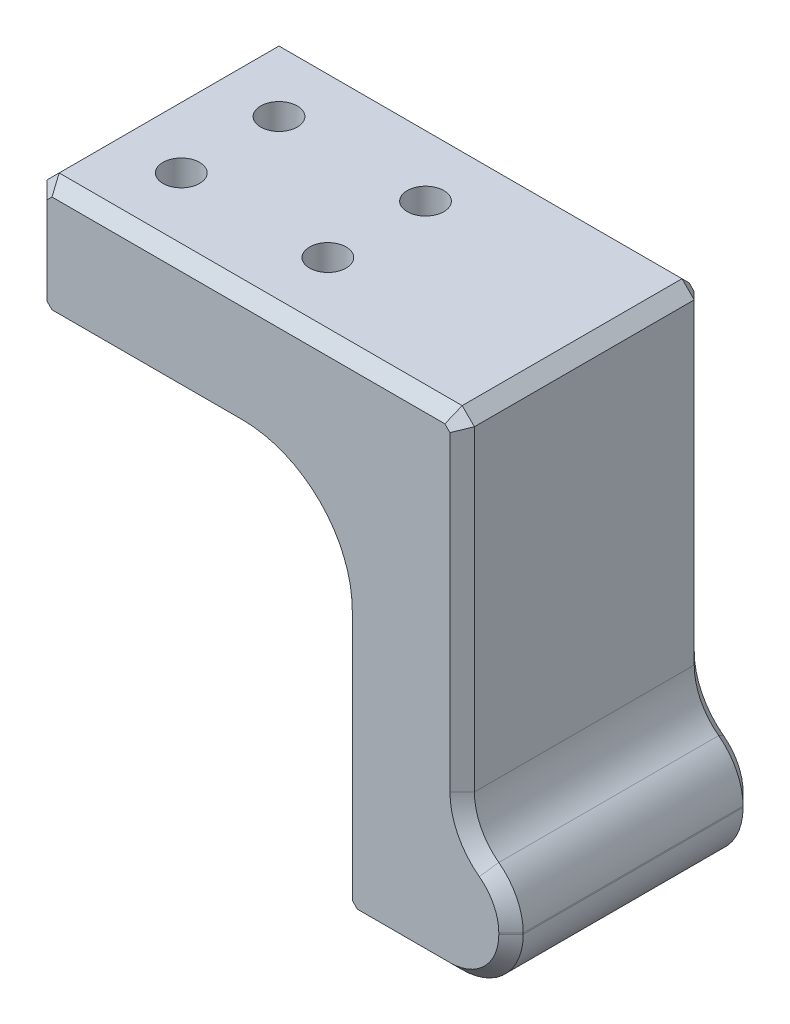
SolidWorks part; units mm, degrees
ref_plane "前视基准面" through (0, 0, 0) normal (0, 0, 1) x (1, 0, 0)
ref_plane "上视基准面" through (0, 0, 0) normal (0, 1, 0) x (1, 0, 0)
ref_plane "右视基准面" through (0, 0, 0) normal (1, 0, 0) x (0, 0, -1)
other "Configuration Table"
sketch "草图5" plane through (0, 0, 0) normal (0, 0, 1) x (1, 0, 0)
  line L13 (-42.5776, 29) -> (47.782, 29) construction
  line L14 (-42.5776, 29) -> (-42.5776, 8) construction
  line L15 (-42.5776, 8) -> (47.782, 8) construction
  line L16 (47.782, 29) -> (47.782, 8) construction
  line L17 (27.782, 7) -> (57.782, 7) construction
  line L18 (27.782, 7) -> (27.782, -23) construction
  line L19 (27.782, -23) -> (57.782, -23) construction
  line L20 (57.782, 7) -> (57.782, -23) construction
  line L34 (-8.4143, 8) -> (26.5857, 8)
  line L47 (26.5857, 8) -> (26.5857, -22)
  line L48 (26.5857, -22) -> (30.5857, -22)
  line L49 (30.5857, -22) -> (30.5857, -32)
  line L50 (30.5857, -32) -> (16.5857, -32)
  line L51 (16.5857, -32) -> (16.5857, -2)
  line L52 (16.5857, -2) -> (-8.4143, -2)
  line L53 (-8.4143, -2) -> (-8.4143, 8)
  dimension "D1" = 30
  dimension "D2" = 30
  dimension "D3" = 1
  dimension "D4" = 21
  dimension "D5" = 10
  dimension "D6" = 10
  dimension "D7" = 25
  dimension "D8" = 35
  dimension "D9" = 30
  dimension "D10" = 10
  dimension "D11" = 4
extrude "凸台-拉伸3" add sketch "草图5" along normal blind 20
fillet "圆角3" radius 5 2 edges at (30.5857, -32, 10) (30.5857, -22, 10)
fillet "圆角4" radius 5 1 edges at (26.5857, -22, 10)
fillet "圆角5" radius 8 1 edges at (16.5857, -2, 10)
sketch "草图6" plane through (0, -2, 0) normal (0, -1, 0) x (-1, 0, 0)
  line L0 (8.4143, -20) -> (8.4143, 0) construction
  line L1 (8.4143, -20) -> (-8.5857, -20) construction
  line L2 (8.4143, 0) -> (-8.5857, 0) construction
  circle A0 centre (2.4143, -14) radius 1.5
  circle A1 centre (2.4143, -6) radius 1.5
  circle A2 centre (-9.5857, -6) radius 1.5
  circle A3 centre (-9.5857, -14) radius 1.5
  dimension "D1" = 3
  dimension "D2" = 3
  dimension "D3" = 3
  dimension "D5" = 6
  dimension "D6" = 6
  dimension "D7" = 6
  dimension "D8" = 6
  dimension "D9" = 12
  dimension "D4" = 0
  dimension "D10" = 3
  dimension "D11" = 0
  dimension "D12" = 0
extrude "切除-拉伸1" cut sketch "草图6" against normal blind 20 and the other way blind 20
chamfer "倒角1" distance 1 angle 45 4 edges at (26.5857, 8, 10) (-8.4143, 8, 10) (-8.4143, -2, 10) (16.5857, -32, 10)
chamfer "倒角2" distance 1 angle 45 30 edges at (-7.9143, 7.5, 0) (-8.4143, 3, 0) (-7.9143, -1.5, 0) (0.5857, -2, 0) (14.2425, -4.3431, 0) (16.5857, -20.5, 0) (17.0857, -31.5, 0) (21.5857, -32, 0) (29.1212, -30.5355, 0) (30.5857, -26.9495, 0) (30.0578, -24.6629, 0) (27.1136, -21.135, 0) (26.5857, -5.9495, 0) (26.0857, 7.5, 0) (9.0857, 8, 0) (27.1136, -21.135, 20) (30.0578, -24.6629, 20) (30.5857, -26.9495, 20) (29.1212, -30.5355, 20) (21.5857, -32, 20) (17.0857, -31.5, 20) (16.5857, -20.5, 20) (14.2425, -4.3431, 20) (0.5857, -2, 20) (-7.9143, -1.5, 20) (-8.4143, 3, 20) (-7.9143, 7.5, 20) (9.0857, 8, 20) (26.0857, 7.5, 20) (26.5857, -5.9495, 20)
